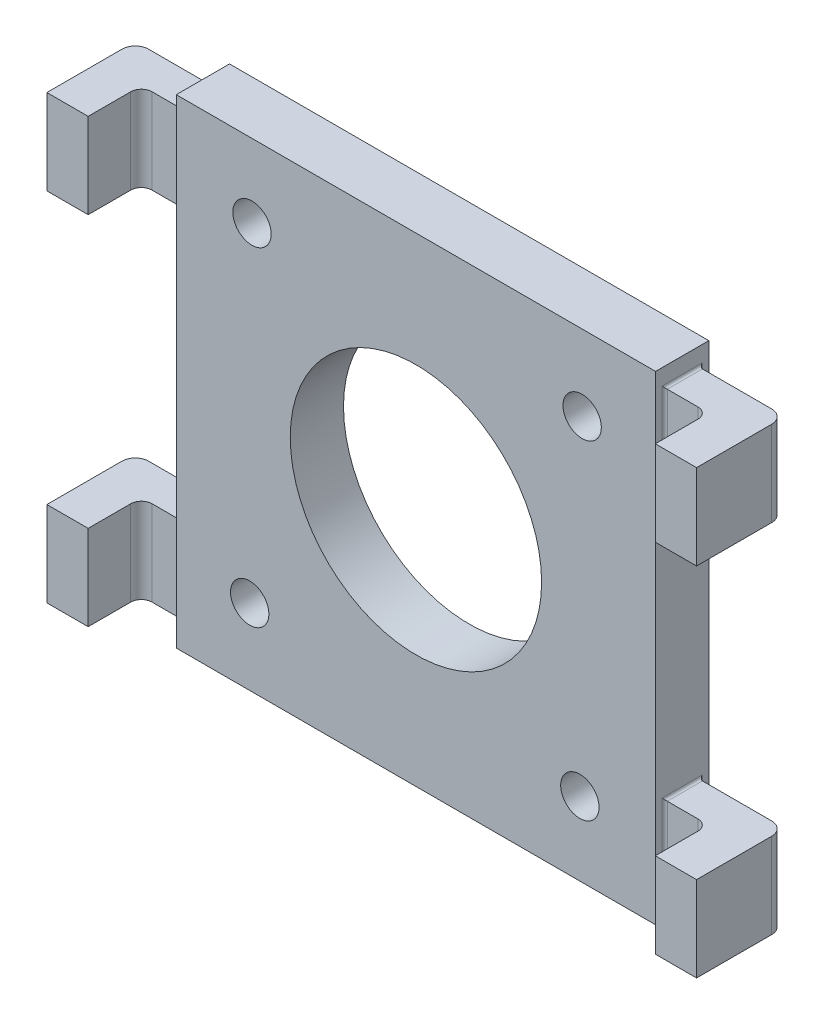
SolidWorks part; units mm, degrees
ref_plane "Front Plane" through (0, 0, 0) normal (0, 0, 1) x (1, 0, 0)
ref_plane "Top Plane" through (0, 0, 0) normal (0, 1, 0) x (1, 0, 0)
ref_plane "Right Plane" through (0, 0, 0) normal (1, 0, 0) x (0, 0, -1)
sketch "Sketch2" plane through (0, 0, 0) normal (0, 0, 1) x (1, 0, 0)
  line L1 (-24.375, 22.5) -> (20.625, 22.5)
  line L2 (-24.375, 22.5) -> (-24.375, -22.5)
  line L3 (-24.375, -22.5) -> (20.625, -22.5)
  line L4 (20.625, 22.5) -> (20.625, -22.5)
  line L5 (-24.375, 22.5) -> (20.625, -22.5) construction
  line L6 (-24.375, -22.5) -> (20.625, 22.5) construction
  circle A0 centre (-17.2671, 15.6071) radius 1.8
  circle A1 centre (-17.4821, -15.3921) radius 1.8
  circle A2 centre (13.5171, -15.6071) radius 1.8
  circle A3 centre (13.7321, 15.3921) radius 1.8
  circle A4 centre (-1.875, 0) radius 11.8
  point P0 (-1.875, 0)
  dimension "D1" = 45
  dimension "D2" = 45
extrude "Boss-Extrude1" add sketch "Sketch2" along normal blind 5
sketch "Sketch3" plane through (-24.375, 0, 0) normal (-1, 0, 0) x (0, 0, 1)
  line L1 (4.15, 20.75) -> (0.85, 20.75)
  line L2 (4.15, 20.75) -> (4.15, 12.75)
  line L3 (4.15, 12.75) -> (0.85, 12.75)
  line L4 (0.85, 20.75) -> (0.85, 12.75)
  line L5 (5, 22.5) -> (0, 22.5) construction
  line L11 (2.75, 0) -> (-2.75, 0) construction
  line L12 (4.15, -12.75) -> (0.85, -12.75)
  line L17 (0.85, -20.75) -> (0.85, -12.75)
  line L18 (4.15, -20.75) -> (0.85, -20.75)
  line L19 (4.15, -20.75) -> (4.15, -12.75)
  point P0 (2.5, 16.75)
  point P5 (2.5524, -16.3405)
extrude "Boss-Extrude2" add sketch "Sketch3" along normal blind 8
fillet "Fillet1" radius 0.25 8 edges at (-24.375, 20.75, 2.5) (-24.375, -12.75, 2.5) (-24.375, -20.75, 2.5) (-24.375, -16.75, 0.85) (-24.375, 12.75, 2.5) (-24.375, 16.75, 0.85) (-24.375, 16.75, 4.15) (-24.375, -16.75, 4.15)
sketch "Sketch4" plane through (0, 0, 4.15) normal (0, 0, 1) x (1, 0, 0)
  line L0 (-32.375, 12.75) -> (-24.625, 12.75) construction
  line L1 (-32.375, 20.75) -> (-28.5, 20.75)
  line L2 (-32.375, 20.75) -> (-32.375, 12.75)
  line L3 (-32.375, 12.75) -> (-28.5, 12.75)
  line L4 (-28.5, 20.75) -> (-28.5, 12.75)
  line L5 (-32.375, -20.75) -> (-24.625, -20.75) construction
  line L6 (-32.375, -12.75) -> (-28.5, -12.75)
  line L7 (-32.375, -12.75) -> (-32.375, -20.75)
  line L8 (-32.375, -20.75) -> (-28.5, -20.75)
  line L9 (-28.5, -12.75) -> (-28.5, -20.75)
extrude "Boss-Extrude3" add sketch "Sketch4" along normal blind 5
fillet "Fillet2" radius 1 2 edges at (-28.5, -16.75, 4.15) (-28.5, 16.75, 4.15)
fillet "Fillet3" radius 1.25 2 edges at (-32.375, -16.75, 0.85) (-32.375, 16.75, 0.85)
sketch "Sketch5" plane through (20.625, 0, 0) normal (1, 0, 0) x (0, 0, -1)
  line L0 (-5, 22.5) -> (0, 22.5) construction
  line L1 (-4.15, 20.75) -> (-0.85, 20.75)
  line L2 (-4.15, 20.75) -> (-4.15, 12.75)
  line L3 (-4.15, 12.75) -> (-0.85, 12.75)
  line L4 (-0.85, 20.75) -> (-0.85, 12.75)
  line L5 (0, -22.5) -> (0, 22.5) construction
  line L8 (5.0325, 0) -> (-5.0325, 0) construction
  line L9 (-4.15, -12.75) -> (-0.85, -12.75)
  line L10 (-0.85, -20.75) -> (-0.85, -12.75)
  line L11 (-4.15, -20.75) -> (-0.85, -20.75)
  line L12 (-4.15, -20.75) -> (-4.15, -12.75)
  dimension "D1" = 1.75
  dimension "D2" = 3.3
  dimension "D3" = 0.85
  dimension "D4" = 8
extrude "Boss-Extrude4" add sketch "Sketch5" along normal blind 8 contours L2 L1 L4 L3 | L9 L10 L11 L12
fillet "Fillet4" radius 0.25 8 edges at (20.625, -12.75, 2.5) (20.625, -16.75, 4.15) (20.625, -20.75, 2.5) (20.625, -16.75, 0.85) (20.625, 20.75, 2.5) (20.625, 12.75, 2.5) (20.625, 16.75, 0.85) (20.625, 16.75, 4.15)
sketch "Sketch6" plane through (0, 0, 4.15) normal (0, 0, 1) x (1, 0, 0)
  line L0 (28.625, 12.75) -> (20.875, 12.75) construction
  line L1 (28.625, 20.75) -> (24.75, 20.75)
  line L2 (28.625, 20.75) -> (28.625, 12.75)
  line L3 (28.625, 12.75) -> (24.75, 12.75)
  line L4 (24.75, 20.75) -> (24.75, 12.75)
  line L5 (28.625, -20.75) -> (20.875, -20.75) construction
  line L6 (28.625, -12.75) -> (24.75, -12.75)
  line L7 (28.625, -12.75) -> (28.625, -20.75)
  line L8 (28.625, -20.75) -> (24.75, -20.75)
  line L9 (24.75, -12.75) -> (24.75, -20.75)
extrude "Boss-Extrude5" add sketch "Sketch6" along normal blind 5
fillet "Fillet5" radius 1 2 edges at (24.75, -16.75, 4.15) (24.75, 16.75, 4.15)
fillet "Fillet6" radius 1.25 2 edges at (28.625, 16.75, 0.85) (28.625, -16.75, 0.85)
